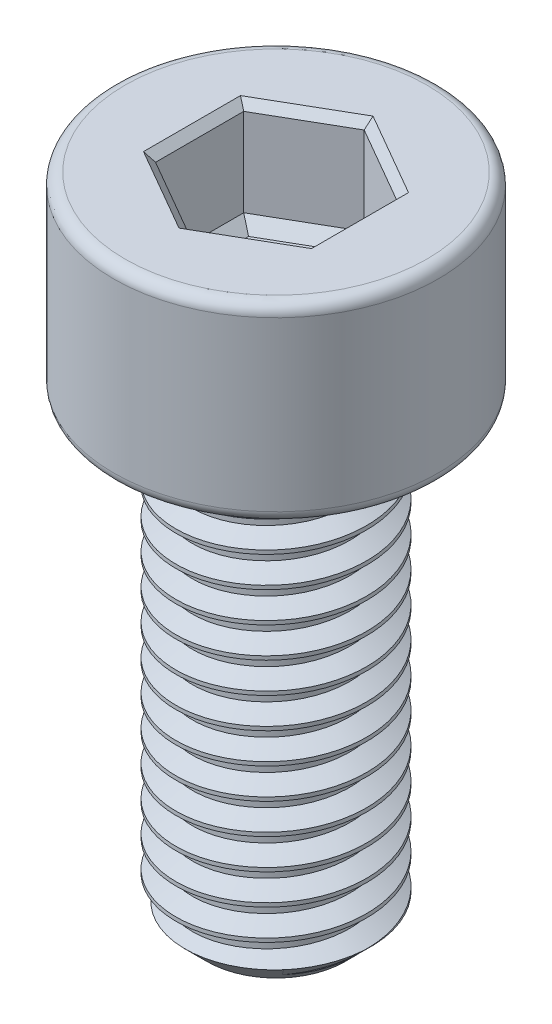
SolidWorks part; units mm, degrees
material "AISI Type A2 Tool Steel"
ref_plane "Front Plane" through (0, 0, 0) normal (0, 0, 1) x (1, 0, 0)
ref_plane "Top Plane" through (0, 0, 0) normal (0, 1, 0) x (1, 0, 0)
ref_plane "Right Plane" through (0, 0, 0) normal (1, 0, 0) x (0, 0, -1)
sketch "Sketch1" plane through (0, 0, 0) normal (0, 1, 0) x (1, 0, 0)
  circle A0 centre (0, 0) radius 2.5
  dimension "D1" = 5
extrude "Boss-Extrude1" add sketch "Sketch1" along normal blind 12
thread "Thread1" pitch 0.8 method cut profile "Thread Profile1" start angle 0, offset 1, length 0, pitch 0.8, diameter 5
ref_plane "Plane1" through (-2.5, 13, 0) normal (0, 0, 1) x (-1, 0, 0)
sketch "Thread Profile1" plane through (-2.5, 13, 0) normal (0, 0, 1) x (-1, 0, 0)
  line L0 (0, 0) -> (0, 0.8) construction
  line L11 (0, 0) -> (0, 0.7)
  line L12 (0, 0.7) -> (-0.433, 0.45)
  line L13 (-0.433, 0.45) -> (-0.433, 0.25)
  line L15 (-0.433, 0.25) -> (0, 0)
  line L17 (-0.433, 0.35) -> (0, 0.35) construction
  point P2 (0, 0)
  dimension "Pitch" = 0.8
  dimension "Profile_Angle" = 60
  dimension "Profile_Land" = 0.2
  dimension "Profile_Height" = 0.433
sketch "Sketch5" plane through (0, 12, 0) normal (0, 1, 0) x (1, 0, 0)
  circle A0 centre (0, 0) radius 4.25
  dimension "D1" = 8.5
extrude "Boss-Extrude2" add sketch "Sketch5" along normal blind 5
fillet "Fillet1" radius 0.3 2 edges at (0, 12, 4.25) (0, 17, 4.25)
sketch "Sketch6" plane through (0, 0, 0) normal (0, 0, 1) x (1, 0, 0)
  line L0 (0, 0) -> (0, 0.2882) construction
  line L1 (0, 0) -> (2.51, 0) construction
  line L2 (2.51, 0) -> (2.51, 0.7)
  line L3 (2.51, 0.7) -> (1.81, 0)
  line L4 (1.81, 0) -> (2.51, 0)
  dimension "D1" = 45
  dimension "D2" = 0.7
  dimension "D3" = 2.51
revolve "Cut-Revolve1" cut sketch "Sketch6" angle 360 about L0
sketch "Sketch7" plane through (0, 17, 0) normal (0, 1, 0) x (1, 0, 0)
  line L1 (0, 2.3094) -> (-2, 1.1547)
  line L2 (-2, 1.1547) -> (-2, -1.1547)
  line L3 (-2, -1.1547) -> (0, -2.3094)
  line L4 (0, -2.3094) -> (2, -1.1547)
  line L5 (2, -1.1547) -> (2, 1.1547)
  line L6 (2, 1.1547) -> (0, 2.3094)
  circle A0 centre (0, 0) radius 2 construction
  dimension "D1" = 4
extrude "Cut-Extrude1" cut sketch "Sketch7" against normal blind 2.5
chamfer "Chamfer1" distance 0.2 angle 45 6 edges at (-2, 17, 0) (-1, 17, 1.7321) (1, 17, 1.7321) (2, 17, 0) (1, 17, -1.7321) (-1, 17, -1.7321)
sketch "Sketch8" plane through (0, 14.5, 0) normal (0, 1, 0) x (1, 0, 0)
  line L1 (0, 2.3094) -> (-2, 1.1547)
  line L2 (-2, 1.1547) -> (-2, -1.1547)
  line L3 (-2, -1.1547) -> (0, -2.3094)
  line L4 (0, -2.3094) -> (2, -1.1547)
  line L5 (2, -1.1547) -> (2, 1.1547)
  line L6 (2, 1.1547) -> (0, 2.3094)
  circle A0 centre (0, 0) radius 2 construction
extrude "Cut-Extrude2" cut sketch "Sketch8" against normal blind 0.3 draft 45
